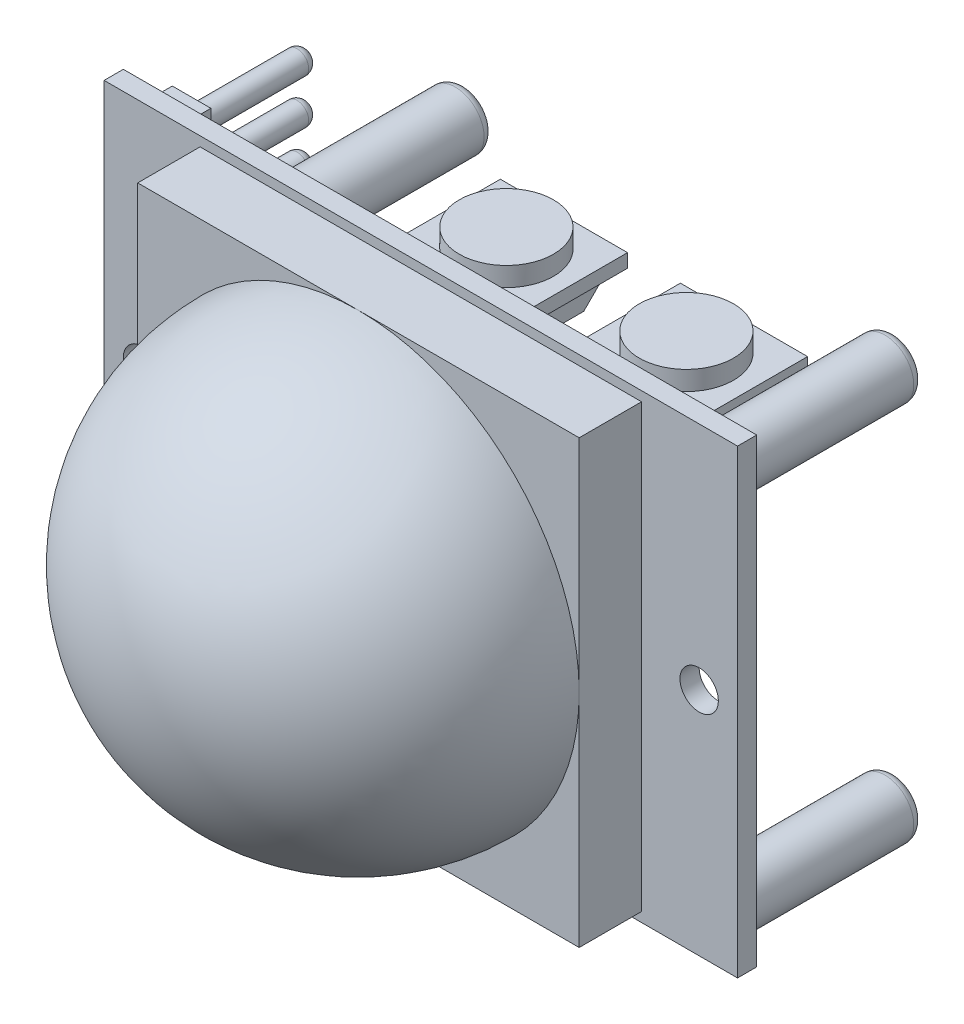
SolidWorks part; units mm, degrees
ref_plane "Front Plane" through (0, 0, 0) normal (0, 0, 1) x (1, 0, 0)
ref_plane "Top Plane" through (0, 0, 0) normal (0, 1, 0) x (1, 0, 0)
ref_plane "Right Plane" through (0, 0, 0) normal (1, 0, 0) x (0, 0, -1)
sketch "Sketch1" plane through (0, 0, 0) normal (0, 0, 1) x (1, 0, 0)
  line L1 (-16.5, -12) -> (16.5, -12)
  line L2 (-16.5, -12) -> (-16.5, 12)
  line L3 (-16.5, 12) -> (16.5, 12)
  line L4 (16.5, -12) -> (16.5, 12)
  line L5 (-16.5, -12) -> (16.5, 12) construction
  line L6 (-16.5, 12) -> (16.5, -12) construction
  point P0 (0, 0)
extrude "Boss-Extrude1" add sketch "Sketch1" along normal blind 1
sketch "Sketch2" plane through (0, 0, 1) normal (0, 0, 1) x (1, 0, 0)
  line L2 (-11.5, -11.5) -> (11.5, -11.5)
  line L3 (-11.5, -11.5) -> (-11.5, 11.5)
  line L4 (-11.5, 11.5) -> (11.5, 11.5)
  line L5 (11.5, -11.5) -> (11.5, 11.5)
  line L6 (-11.5, -11.5) -> (11.5, 11.5) construction
  line L7 (-11.5, 11.5) -> (11.5, -11.5) construction
  point P0 (0, 0)
extrude "Boss-Extrude2" add sketch "Sketch2" along normal blind 3.25
sketch "Sketch3" plane through (0, 0, 4.25) normal (0, 0, 1) x (1, 0, 0)
  circle A0 centre (0, 0) radius 11.5
extrude "Boss-Extrude3" add sketch "Sketch3" along normal blind 11.5
fillet "Fillet1" radius 11.5 1 edges at (11.5, 0, 15.75)
sketch "Sketch4" plane through (0, 0, 1) normal (0, 0, 1) x (1, 0, 0)
  circle A0 centre (14.5, 0) radius 1
  circle A1 centre (-14.5, 0) radius 1
extrude "Cut-Extrude1" cut sketch "Sketch4" against normal blind 11.5
sketch "Sketch5" plane through (0, 0, 0) normal (0, 0, -1) x (-1, 0, 0)
  circle A0 centre (-14.6821, 9.8484) radius 1.5
  circle A1 centre (-14.6821, -10.0035) radius 1.5
  circle A2 centre (14.0617, -10.0035) radius 1.5
  circle A3 centre (7.7029, 9.8484) radius 1.5
extrude "Boss-Extrude4" add sketch "Sketch5" along normal blind 9
sketch "Sketch6" plane through (0, 0, 0) normal (0, 0, -1) x (-1, 0, 0)
  line L4 (15.4488, 11.0216) -> (13.4382, 11.0216)
  line L5 (15.4488, 11.0216) -> (15.4488, 4.0261)
  line L6 (15.4488, 4.0261) -> (13.4382, 4.0261)
  line L7 (3.5, -10) -> (-3.5, -10)
  line L8 (3.5, -10) -> (3.5, -8)
  line L9 (3.5, -8) -> (-3.5, -8)
  line L10 (-3.5, -10) -> (-3.5, -8)
  line L11 (13.4382, 11.0216) -> (13.4382, 4.0261)
  line L13 (-7.0234, 9.0109) -> (-9.0234, 9.5973) construction
  line L14 (-7.0234, 9.5973) -> (-9.0234, 9.0109) construction
  line L15 (-9.0234, 9.5973) -> (-9.0234, 9.0109)
  line L16 (0.0443, 9.5973) -> (2.0443, 9.5973)
  line L17 (0.0443, 9.5973) -> (0.0443, 9.0109)
  line L18 (0.0443, 9.0109) -> (2.0443, 9.0109)
  line L19 (2.0443, 9.5973) -> (2.0443, 9.0109)
  line L20 (0.0443, 9.5973) -> (2.0443, 9.0109) construction
  line L21 (0.0443, 9.0109) -> (2.0443, 9.5973) construction
  line L22 (-7.0234, 9.0109) -> (-9.0234, 9.0109)
  line L23 (-7.0234, 9.5973) -> (-7.0234, 9.0109)
  line L24 (-7.0234, 9.5973) -> (-9.0234, 9.5973)
  point P26 (1.0443, 9.3041)
  point P34 (-8.3358, 9.3041)
extrude "Boss-Extrude5" add sketch "Sketch6" along normal blind 1.5
sketch "Sketch9" plane through (0, 0, -1.5) normal (0, 0, -1) x (-1, 0, 0)
  line L0 (0.0443, 9.0109) -> (2.0443, 9.0109) construction
  line L12 (-2.2695, 9.3627) -> (4.358, 9.3627)
  line L13 (-2.2695, 9.3627) -> (-2.2695, 8.6591)
  line L14 (-2.2695, 8.6591) -> (4.358, 8.6591)
  line L15 (4.358, 9.3627) -> (4.358, 8.6591)
  line L16 (-2.2695, 9.3627) -> (4.358, 8.6591) construction
  line L17 (-2.2695, 8.6591) -> (4.358, 9.3627) construction
  line L18 (-5.0221, 8.6591) -> (-11.6496, 8.6591)
  line L19 (-11.6496, 9.3627) -> (-11.6496, 8.6591)
  line L20 (-5.0221, 9.3627) -> (-11.6496, 9.3627)
  line L21 (-5.0221, 9.3627) -> (-5.0221, 8.6591)
  line L22 (-5.0221, 8.6591) -> (-11.6496, 9.3627) construction
  line L23 (-5.0221, 9.3627) -> (-11.6496, 8.6591) construction
  circle A0 centre (0, -9) radius 0.6
  circle A1 centre (-2.35, -9) radius 0.6
  circle A2 centre (2.35, -9) radius 0.6
  circle A3 centre (14.4435, 7.5238) radius 0.6
  circle A4 centre (14.4435, 9.8566) radius 0.6
  circle A5 centre (14.4435, 5.1911) radius 0.6
  point P0 (1.0443, 9.0109)
  point P25 (-8.3358, 9.0109)
extrude "Boss-Extrude6" add sketch "Sketch9" along normal blind 6
fillet "Fillet2" radius 0.5 10 edges at (-15.0435, 9.8566, -7.5) (-15.0435, 7.5238, -7.5) (-13.8435, 5.1911, -7.5) (-1.75, -9, -7.5) (-0.6, -9, -7.5) (1.75, -9, -7.5) (-15.5617, -10.0035, -9) (-9.2029, 9.8484, -9) (13.1821, -10.0035, -9) (13.1821, 9.8484, -9)
sketch "Sketch10" plane through (0, 8.6591, 0) normal (0, -1, 0) x (1, 0, 0)
  line L1 (11.268, -6.9124) -> (5.4114, -6.9124)
  line L2 (11.268, -6.9124) -> (11.268, -2.19)
  line L3 (11.268, -2.19) -> (5.4114, -2.19)
  line L4 (5.4114, -6.9124) -> (5.4114, -2.19)
  line L5 (1.5746, -6.9124) -> (-4.2436, -6.9124)
  line L6 (1.5746, -6.9124) -> (1.5746, -2.19)
  line L7 (1.5746, -2.19) -> (-4.2436, -2.19)
  line L8 (-4.2436, -6.9124) -> (-4.2436, -2.19)
extrude "Boss-Extrude7" add sketch "Sketch10" along normal blind 1.5
chamfer "Chamfer1" distance 1 angle 45 4 edges at (-1.3345, 7.1591, -2.19) (-1.3345, 7.1591, -6.9124) (8.3397, 7.1591, -2.19) (8.3397, 7.1591, -6.9124)
sketch "Sketch11" plane through (0, 9.3627, 0) normal (0, 1, 0) x (1, 0, 0)
  circle A0 centre (-1.0443, 4.5) radius 2.4552
  circle A1 centre (8.3358, 4.5) radius 2.4552
extrude "Boss-Extrude8" add sketch "Sketch11" along normal blind 1
sketch "Sketch12" plane through (0, 0, 0) normal (0, 0, -1) x (-1, 0, 0)
  line L0 (-12.0092, 4.7998) -> (-9.5092, 4.7998)
  line L1 (-15.5092, 4.7998) -> (-13.0092, 4.7998)
  line L2 (-15.5092, 4.7998) -> (-15.5092, 3.7998)
  line L3 (-15.5092, 3.7998) -> (-13.0092, 3.7998)
  line L4 (-13.0092, 4.7998) -> (-13.0092, 3.7998)
  line L5 (-12.0092, 4.7998) -> (-12.0092, 3.7998)
  line L6 (-12.0092, 3.7998) -> (-9.5092, 3.7998)
  line L7 (-9.5092, 4.7998) -> (-9.5092, 3.7998)
  line L8 (-8.5092, 4.7998) -> (-6.0092, 4.7998)
  line L9 (-8.5092, 4.7998) -> (-8.5092, 3.7998)
  line L10 (-8.5092, 3.7998) -> (-6.0092, 3.7998)
  line L11 (-6.0092, 4.7998) -> (-6.0092, 3.7998)
  line L12 (-5.0092, 4.7998) -> (-2.5092, 4.7998)
  line L13 (-5.0092, 4.7998) -> (-5.0092, 3.7998)
  line L14 (-5.0092, 3.7998) -> (-2.5092, 3.7998)
  line L15 (-2.5092, 4.7998) -> (-2.5092, 3.7998)
  line L16 (-1.5092, 4.7998) -> (0.9908, 4.7998)
  line L17 (-1.5092, 4.7998) -> (-1.5092, 3.7998)
  line L18 (-1.5092, 3.7998) -> (0.9908, 3.7998)
  line L19 (0.9908, 4.7998) -> (0.9908, 3.7998)
  line L20 (5.4908, 6.2998) -> (7.9908, 6.2998)
  line L21 (5.4908, 6.2998) -> (5.4908, 5.2998)
  line L22 (5.4908, 5.2998) -> (7.9908, 5.2998)
  line L23 (7.9908, 6.2998) -> (7.9908, 5.2998)
  line L24 (5.4908, 4.7998) -> (7.9908, 4.7998)
  line L25 (5.4908, 4.7998) -> (5.4908, 3.7998)
  line L26 (5.4908, 3.7998) -> (7.9908, 3.7998)
  line L27 (7.9908, 4.7998) -> (7.9908, 3.7998)
  line L28 (8.9908, 4.7998) -> (11.4908, 4.7998)
  line L29 (8.9908, 4.7998) -> (8.9908, 3.7998)
  line L30 (8.9908, 3.7998) -> (11.4908, 3.7998)
  line L31 (11.4908, 4.7998) -> (11.4908, 3.7998)
  line L32 (1.9908, 4.7998) -> (4.4908, 4.7998) [skipped]
  line L33 (1.9908, 4.7998) -> (1.9908, 3.7998) [skipped]
  line L34 (1.9908, 3.7998) -> (4.4908, 3.7998) [skipped]
  line L35 (4.4908, 4.7998) -> (4.4908, 3.7998) [skipped]
  line L36 (8.9908, 6.2998) -> (11.4908, 6.2998)
  line L37 (8.9908, 6.2998) -> (8.9908, 5.2998)
  line L38 (8.9908, 5.2998) -> (11.4908, 5.2998)
  line L39 (11.4908, 6.2998) -> (11.4908, 5.2998)
  line L40 (-6.0826, -2.3013) -> (-7.0826, -2.3013)
  line L41 (5.8935, 2.4556) -> (10.7531, 2.4556)
  line L42 (5.8935, 2.4556) -> (5.8935, -6.6948)
  line L43 (5.8935, -6.6948) -> (10.7531, -6.6948)
  line L44 (10.7531, 2.4556) -> (10.7531, -6.6948)
  line L45 (-6.0826, 1.6987) -> (-7.0826, 1.6987)
  line L46 (-6.0826, 1.6987) -> (-6.0826, -0.8013)
  line L47 (-6.0826, -0.8013) -> (-7.0826, -0.8013)
  line L48 (-7.0826, 1.6987) -> (-7.0826, -0.8013)
  line L49 (-6.0826, -2.3013) -> (-6.0826, -4.8013)
  line L50 (-6.0826, -4.8013) -> (-7.0826, -4.8013)
  line L51 (-7.0826, -2.3013) -> (-7.0826, -4.8013)
  line L52 (-7.5826, -2.3013) -> (-8.5826, -2.3013)
  line L53 (-7.5826, -2.3013) -> (-7.5826, -4.8013)
  line L54 (-7.5826, -4.8013) -> (-8.5826, -4.8013)
  line L55 (-8.5826, -2.3013) -> (-8.5826, -4.8013)
  line L57 (-14.0617, -4.2002) -> (-9.9776, -4.2002)
  line L58 (-14.0617, -4.2002) -> (-14.0617, -6.2002)
  line L59 (-14.0617, -6.2002) -> (-9.9776, -6.2002)
  line L60 (-9.9776, -4.2002) -> (-9.9776, -6.2002)
  line L72 (-5.0092, -1.2002) -> (-2.5092, -1.2002)
  line L73 (-5.0092, -1.2002) -> (-5.0092, -2.2002)
  line L74 (-5.0092, -2.2002) -> (-2.5092, -2.2002)
  line L75 (-2.5092, -1.2002) -> (-2.5092, -2.2002)
  line L80 (-5.0092, -3.2002) -> (-2.5092, -3.2002)
  line L81 (-5.0092, -3.2002) -> (-5.0092, -4.2002)
  line L82 (-5.0092, -4.2002) -> (-2.5092, -4.2002)
  line L83 (-2.5092, -3.2002) -> (-2.5092, -4.2002)
  line L84 (-1.5092, -3.2002) -> (0.9908, -3.2002)
  line L85 (-1.5092, -3.2002) -> (-1.5092, -4.2002)
  line L86 (-1.5092, -4.2002) -> (0.9908, -4.2002)
  line L87 (0.9908, -3.2002) -> (0.9908, -4.2002)
  line L92 (-1.5092, -5.2002) -> (0.9908, -5.2002)
  line L93 (-1.5092, -5.2002) -> (-1.5092, -6.2002)
  line L94 (-1.5092, -6.2002) -> (0.9908, -6.2002)
  line L95 (0.9908, -5.2002) -> (0.9908, -6.2002)
  line L96 (-5.0092, 2.7998) -> (-2.5092, 2.7998) [skipped]
  line L97 (-5.0092, 2.7998) -> (-5.0092, 1.7998) [skipped]
  line L98 (-5.0092, 1.7998) -> (-2.5092, 1.7998) [skipped]
  line L99 (-2.5092, 2.7998) -> (-2.5092, 1.7998) [skipped]
  line L100 (-5.0092, 0.7998) -> (-2.5092, 0.7998) [skipped]
  line L101 (-5.0092, 0.7998) -> (-5.0092, -0.2002) [skipped]
  line L102 (-5.0092, -0.2002) -> (-2.5092, -0.2002) [skipped]
  line L103 (-2.5092, 0.7998) -> (-2.5092, -0.2002) [skipped]
  line L104 (-1.5092, 2.7998) -> (0.9908, 2.7998) [skipped]
  line L105 (-1.5092, 2.7998) -> (-1.5092, 1.7998) [skipped]
  line L106 (-1.5092, 1.7998) -> (0.9908, 1.7998) [skipped]
  line L107 (0.9908, 2.7998) -> (0.9908, 1.7998) [skipped]
  line L108 (-1.5092, 0.7998) -> (0.9908, 0.7998) [skipped]
  line L109 (-1.5092, 0.7998) -> (-1.5092, -0.2002) [skipped]
  line L110 (-1.5092, -0.2002) -> (0.9908, -0.2002) [skipped]
  line L111 (0.9908, 0.7998) -> (0.9908, -0.2002) [skipped]
  line L112 (-1.5092, -1.2002) -> (0.9908, -1.2002) [skipped]
  line L113 (-1.5092, -1.2002) -> (-1.5092, -2.2002) [skipped]
  line L114 (-1.5092, -2.2002) -> (0.9908, -2.2002) [skipped]
  line L115 (0.9908, -1.2002) -> (0.9908, -2.2002) [skipped]
  line L116 (-5.0092, -5.2002) -> (-2.5092, -5.2002) [skipped]
  line L117 (-5.0092, -5.2002) -> (-5.0092, -6.2002) [skipped]
  line L118 (-5.0092, -6.2002) -> (-2.5092, -6.2002) [skipped]
  line L119 (-2.5092, -5.2002) -> (-2.5092, -6.2002) [skipped]
  dimension "D1" = 8
  dimension "D3" = 2
  dimension "D2" = 2
  dimension "D4" = 2
  dimension "D5" = 6
extrude "Boss-Extrude9" add sketch "Sketch12" along normal blind 0.5
